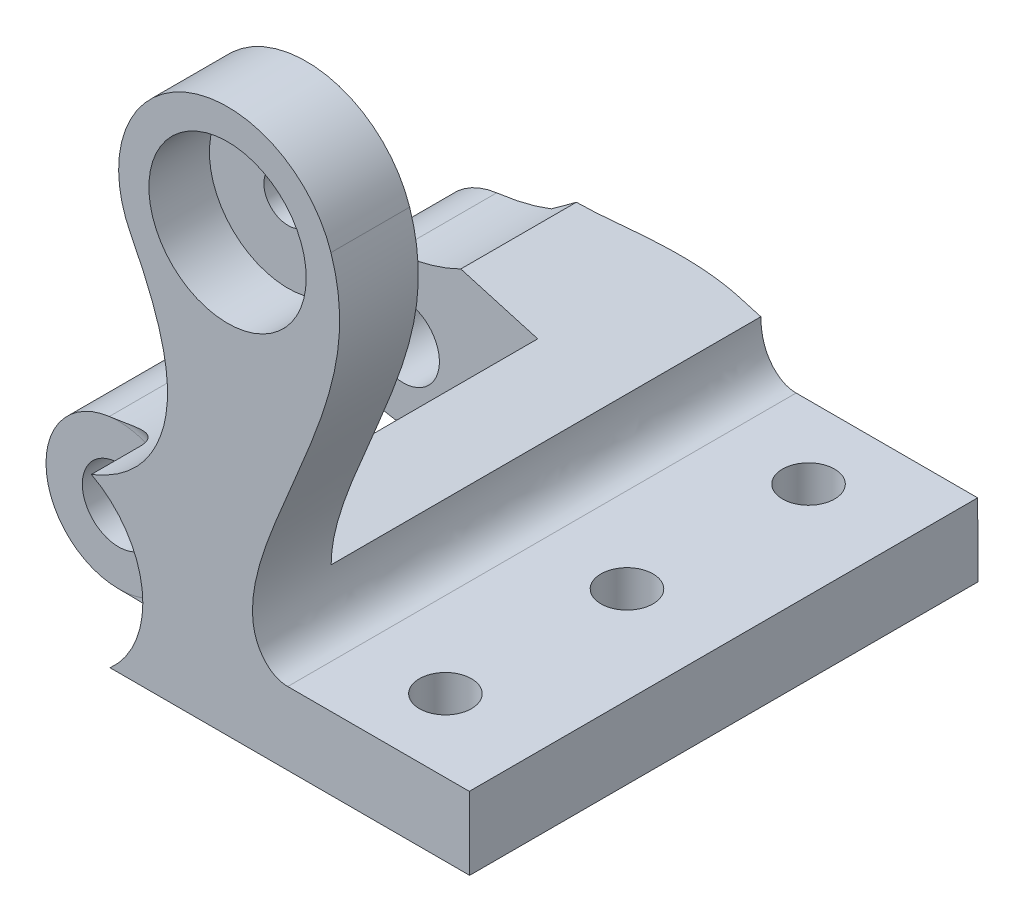
SolidWorks part; units mm, degrees
ref_plane "Front" through (0, 0, 0) normal (0, 0, 1) x (1, 0, 0)
ref_plane "Top" through (0, 0, 0) normal (0, 1, 0) x (1, 0, 0)
ref_plane "Right" through (0, 0, 0) normal (1, 0, 0) x (0, 0, -1)
sketch "Sketch1" plane through (0, 0, 0) normal (0, 0, 1) x (1, 0, 0)
  line L0 (-106.6231, 0) -> (184.6312, 0) construction
  line L1 (0, 98.035) -> (0, -93.0774) construction
  line L2 (-6.0068, 22.0333) -> (-10.1319, 29.9877) construction
  line L3 (-20.2608, 5.3703) -> (-10.1583, 6.6752) construction
  line L4 (-15, -6) -> (20, -6)
  line L5 (20, -6) -> (19.9722, 0)
  line L6 (19.9722, 0) -> (4.9722, 0)
  line L7 (5.6858, 0) -> (4.2587, 0) construction
  line L8 (9.1185, 31.0959) -> (7.9524, 34.6125) construction
  circle A0 centre (-15, 0) radius 3
  circle A1 centre (0, 30) radius 2
  circle A2 centre (0, 30) radius 6.5
  arc A3 (8.5426, 32.8328) -> (-7.9895, 25.8567) centre (0, 30) ccw
  arc A4 (-15.7686, 5.9506) -> (-15, -6) centre (-15, 0) ccw
  spline S0 degree 3 poles (-7.9895, 25.8567) (-4.9067, 19.9121) (-3.6629, 12.1959) (-9.7937, 6.7223) (-15.7686, 5.9506) knots 0 0 0 0 0.536541 1 1 1 1
  spline S1 degree 3 poles (8.5426, 32.8328) (10.6867, 26.367) (5.8561, 16.5236) (0.5084, 2.5146) (4.0803, 0) (4.9722, 0) knots 0 0 0 0 0.582614 0.921224 1 1 1 1
  point P10 (0, 0)
  point P28 (0, 0)
  point P31 (4.5383, 12.6917)
  dimension "D1" = 6
  dimension "D2" = 4
  dimension "D3" = 13
  dimension "D4" = 9
  dimension "D5" = 6
  dimension "D6" = 15
  dimension "D7" = 30
  dimension "D8" = 35
  dimension "D9" = 6.0001
  dimension "D10" = 15
extrude "Boss-Extrude1" add sketch "Sketch1" along normal mid plane 42 contours S1 A3 S0 A4 L4 L5 L6 A2 A0 | A2 A1 region at (-1.1876, 9.3502, 0) region at (-6.3162, 30, 0)
sketch "Sketch2" plane through (0, 0, -21) normal (0, 0, -1) x (-1, 0, 0)
  line L0 (10.2313, 7.5237) -> (-2.0574, 4)
  line L1 (-19.9722, 0) -> (-4.9722, 0) construction
  line L3 (-4.9722, 0) -> (-19.9722, 0)
  line L4 (-19.9722, 0) -> (-20, -6)
  line L5 (-20, -6) -> (15, -6)
  arc A2 (15, -6) -> (15.7686, 5.9506) centre (15, 0) ccw
  arc A3 (7.9895, 25.8567) -> (-8.5426, 32.8328) centre (0, 30) ccw
  arc A5 (7.9895, 25.8567) -> (-8.5426, 32.8328) centre (0, 30) ccw
  spline S2 degree 3 poles (1924.227, 545.7884) (-47.5375, 56.2577) (-25.419, 67.7705) (6.4354, -15.6753) (-82.474, 16.6057) (-275.7639, 1980.5352) knots -3.658141 -3.658141 -3.658141 -3.658141 0.582614 0.921224 2.298449 2.298449 2.298449 2.298449 only from (-8.5426, 32.8328) to (-4.9722, 0)
  spline S3 degree 3 poles (1697.9337, 1085.1183) (166.0687, -2.204) (-179.628, -33.7994) (215.2398, 159.8173) (1033.4927, 1740.8444) knots -3.846488 -3.846488 -3.846488 -3.846488 0.463459 6.174518 6.174518 6.174518 6.174518 only from (15.7686, 5.9506) to (7.9895, 25.8567)
  spline S4 degree 3 poles (-8.5426, 32.8328) (-10.6867, 26.367) (-6.4075, 17.6471) (-2.053, 6.5242) (-2.0574, 4) knots 0 0 0 0 0.582614 0.81608 0.81608 0.81608 0.81608
  spline S5 degree 3 poles (10.2313, 7.5237) (7.8636, 8.719) (3.8819, 13.5543) (4.9067, 19.9121) (7.9895, 25.8567) knots 0.176047 0.176047 0.176047 0.176047 0.463459 1 1 1 1
  dimension "D2" = 16
  dimension "D3" = 4
  dimension "D1" = 0
extrude "Cut-Extrude1" cut sketch "Sketch2" against normal blind 35.5
sketch "Sketch3" plane through (0, 0, 21) normal (0, 0, 1) x (1, 0, 0)
  line L3 (-15, -6) -> (20, -6)
  line L4 (20, -6) -> (19.9722, 0)
  line L5 (19.9722, 0) -> (4.9722, 0)
  line L6 (-15, -6) -> (-4.0341, -6)
  arc A0 (-4.0341, -6) -> (-7.2344, 9.7951) centre (-15, 0) ccw
  arc A2 (8.5426, 32.8328) -> (-7.9895, 25.8567) centre (0, 30) ccw
  arc A3 (-15.7686, 5.9506) -> (-15, -6) centre (-15, 0) ccw
  arc A5 (-15.7686, 5.9506) -> (-15, -6) centre (-15, 0) ccw
  spline S2 degree 3 poles (170.073, 986.2696) (55.4205, 7.3651) (-4.8971, -11.6457) (20.8192, 55.7208) (39.1449, 57.9131) (-953.7165, 304.9354) knots -1.010801 -1.010801 -1.010801 -1.010801 0.078776 0.417386 3.798003 3.798003 3.798003 3.798003 only from (4.9722, 0) to (8.5426, 32.8328)
  spline S3 degree 3 poles (-2328.6093, 4446.4826) (-434.6918, 260.2027) (351.22, -81.2113) (-299.2978, 14.2051) (-4121.1368, 2853.3479) knots -7.467258 -7.467258 -7.467258 -7.467258 0.536541 6.4891 6.4891 6.4891 6.4891 only from (-7.9895, 25.8567) to (-15.7686, 5.9506)
  spline S5 degree 3 poles (-7.2344, 9.7951) (-8.8726, 7.9315) (-11.5334, 6.4976) (-15.7686, 5.9506) knots 0.671484 0.671484 0.671484 0.671484 1 1 1 1
  dimension "D2" = 25
  dimension "D1" = 0
extrude "Cut-Extrude2" cut sketch "Sketch3" against normal blind 15.3 from offset 14.2 offset against normal yes
sketch "Sketch4" plane through (0, 0, 0) normal (0, 1, 0) x (1, 0, 0)
  line L0 (-28.4387, 0) -> (30.7335, 0) construction
  line L1 (12, 18.7695) -> (12, -19.9653) construction
  circle A0 centre (12, 0) radius 2.15
  circle A1 centre (12, 15) radius 2.15
  circle A2 centre (12, -15) radius 2.15
  dimension "D1" = 4.3
  dimension "D3" = 4.3
  dimension "D2" = 12
  dimension "D4" = 15
extrude "Cut-Extrude3" cut sketch "Sketch4" against normal blind 15.3
sketch "Sketch6" plane through (0, 0, 21) normal (0, 0, 1) x (1, 0, 0)
  circle A0 centre (0, 30) radius 6.5
  dimension "D1" = 13
extrude "Cut-Extrude4" cut sketch "Sketch6" against normal blind 5
sketch "Sketch7" plane through (0, 0, 21) normal (0, 0, 1) x (1, 0, 0)
  circle A0 centre (-15, 0) radius 8
  dimension "D1" = 16
extrude "Cut-Extrude5" cut sketch "Sketch7" against normal blind 6
sketch "Sketch8" plane through (0, 0, -21) normal (0, 0, -1) x (-1, 0, 0)
  circle A0 centre (15, 0) radius 8
  dimension "D1" = 16
extrude "Cut-Extrude6" cut sketch "Sketch8" against normal blind 4
fillet "Fillet1" radius 10 1 edges at (-7.055, 0.9363, -21)
fillet "Fillet3" radius 2 1 edges at (-7.055, 0.9363, 15)
